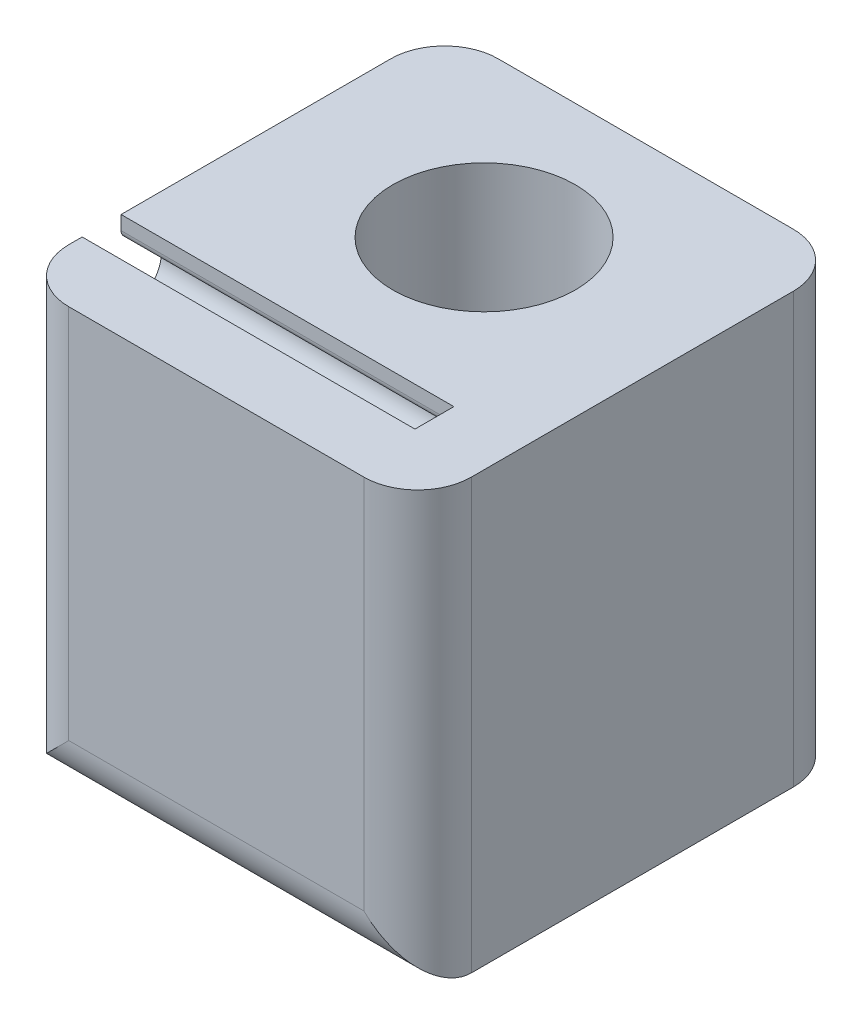
SolidWorks part; units mm, degrees
ref_plane "Front Plane" through (0, 0, 0) normal (0, 0, 1) x (1, 0, 0)
ref_plane "Top Plane" through (0, 0, 0) normal (0, 1, 0) x (1, 0, 0)
ref_plane "Right Plane" through (0, 0, 0) normal (1, 0, 0) x (0, 0, -1)
sketch "Sketch1" plane through (0, 0, 0) normal (1, 0, 0) x (0, 0, -1)
  line L1 (-4, -4) -> (4, -4)
  line L2 (-4, -4) -> (-4, 4)
  line L3 (-4, 4) -> (4, 4)
  line L4 (4, -4) -> (4, 4)
  line L5 (-4, -4) -> (4, 4) construction
  line L6 (-4, 4) -> (4, -4) construction
  point P0 (0, 0)
  dimension "D1" = 8
  dimension "D2" = 8
extrude "Boss-Extrude1" add sketch "Sketch1" along normal blind 7.5
sketch "Sketch2" plane through (0, 0, 0) normal (1, 0, 0) x (0, 0, -1)
  line L0 (-2.025, 4) -> (-2.025, 3.7402)
  line L1 (4, 4) -> (-4, 4) construction
  line L2 (-1.275, 3) -> (-2.025, 3) construction
  line L4 (-2.025, 2) -> (-2.025, 2.2598)
  line L5 (-2.75, 4) -> (-2.75, -4)
  line L6 (-4, -4) -> (4, -4) construction
  line L7 (-2.025, 4) -> (-2.75, 4)
  line L8 (-4, 4) -> (-4, -4) construction
  line L9 (-2.025, 2) -> (-2.025, 1.7402)
  line L10 (-2.025, 0) -> (-2.025, 0.2598)
  line L11 (-1.275, 1) -> (-2.025, 1) construction
  line L12 (-2.025, 0) -> (-2.025, -0.2598)
  line L13 (-2.025, -2) -> (-2.025, -1.7402)
  line L14 (-1.275, -1) -> (-2.025, -1) construction
  line L15 (-2.025, -2) -> (-2.025, -2.2598)
  line L16 (-2.025, -4) -> (-2.025, -3.7402)
  line L17 (-1.275, -3) -> (-2.025, -3) construction
  line L18 (-2.025, -4) -> (-2.75, -4)
  arc A0 (-2.025, 3.7402) -> (-1.8946, 3.5915) centre (-1.875, 3.7402) ccw
  arc A1 (-1.8946, 3.5915) -> (-1.5868, 3.4989) centre (-2.025, 2.6) cw
  arc A2 (-1.5868, 3.4989) -> (-1.5868, 2.5011) centre (-1.83, 3) cw
  arc A3 (-2.025, 2.2598) -> (-1.8946, 2.4085) centre (-1.875, 2.2598) cw
  arc A4 (-1.8946, 2.4085) -> (-1.5868, 2.5011) centre (-2.025, 3.4) ccw
  arc A5 (-2.025, 1.7402) -> (-1.8946, 1.5915) centre (-1.875, 1.7402) ccw
  arc A6 (-1.8946, 1.5915) -> (-1.5868, 1.4989) centre (-2.025, 0.6) cw
  arc A7 (-1.5868, 1.4989) -> (-1.5868, 0.5011) centre (-1.83, 1) cw
  arc A8 (-2.025, 0.2598) -> (-1.8946, 0.4085) centre (-1.875, 0.2598) cw
  arc A9 (-1.8946, 0.4085) -> (-1.5868, 0.5011) centre (-2.025, 1.4) ccw
  arc A10 (-2.025, -0.2598) -> (-1.8946, -0.4085) centre (-1.875, -0.2598) ccw
  arc A11 (-1.8946, -0.4085) -> (-1.5868, -0.5011) centre (-2.025, -1.4) cw
  arc A12 (-1.5868, -0.5011) -> (-1.5868, -1.4989) centre (-1.83, -1) cw
  arc A13 (-2.025, -1.7402) -> (-1.8946, -1.5915) centre (-1.875, -1.7402) cw
  arc A14 (-1.8946, -1.5915) -> (-1.5868, -1.4989) centre (-2.025, -0.6) ccw
  arc A15 (-2.025, -2.2598) -> (-1.8946, -2.4085) centre (-1.875, -2.2598) ccw
  arc A16 (-1.8946, -2.4085) -> (-1.5868, -2.5011) centre (-2.025, -3.4) cw
  arc A17 (-1.5868, -2.5011) -> (-1.5868, -3.4989) centre (-1.83, -3) cw
  arc A18 (-2.025, -3.7402) -> (-1.8946, -3.5915) centre (-1.875, -3.7402) cw
  arc A19 (-1.8946, -3.5915) -> (-1.5868, -3.4989) centre (-2.025, -2.6) ccw
  dimension "D1" = 0.555
  dimension "D2" = 1
  dimension "D3" = 0.15
  dimension "D4" = 0.75
  dimension "D5" = 0.4
  dimension "D6" = 1
  dimension "D7" = 0.725
  dimension "D8" = 1.25
  dimension "D10" = 2
  dimension "D11" = 1.475
  dimension "D9" = 4
extrude "Cut-Extrude1" cut sketch "Sketch2" along normal blind 6.2
hole_wizard "M3 Clearance Hole1" positions "Sketch5" profile "Sketch4" hole size "M3" standard "ANSI Metric" end condition through all
sketch "Sketch5" plane through (0, 4, 0) normal (0, 1, 0) x (1, 0, 0)
  line L0 (0, 4) -> (0, -2.025) construction
  line L1 (7.5, 4) -> (0, 4) construction
  point P0 (3.75, 0.9875)
  point P9 (3.75, 4)
  point P10 (0, 0.9875)
sketch "Sketch4" plane through (3.75, 4, -0.9875) normal (1, 0, 0) x (0, 0, 1)
  line L0 (0, 0) -> (0, 8)
  line L1 (0, 8) -> (1.7, 8)
  line L2 (1.7, 8) -> (1.7, 0)
  line L5 (1.7, 0) -> (0, 0)
  line L11 (0, -6.35) -> (0, 107.95) construction
  dimension "Thru Hole Dia." = 3.4
  dimension "Thru Hole Depth" = 8
fillet "Fillet1" radius 1 5 edges at (3.75, -4, 4) (7.5, 0, 4) (7.5, 0, -4) (0, 0, -4) (0, 0, 4)
ref_plane "Plane1" through (0, 4, 0) normal (0, 1, 0) x (1, 0, 0)
